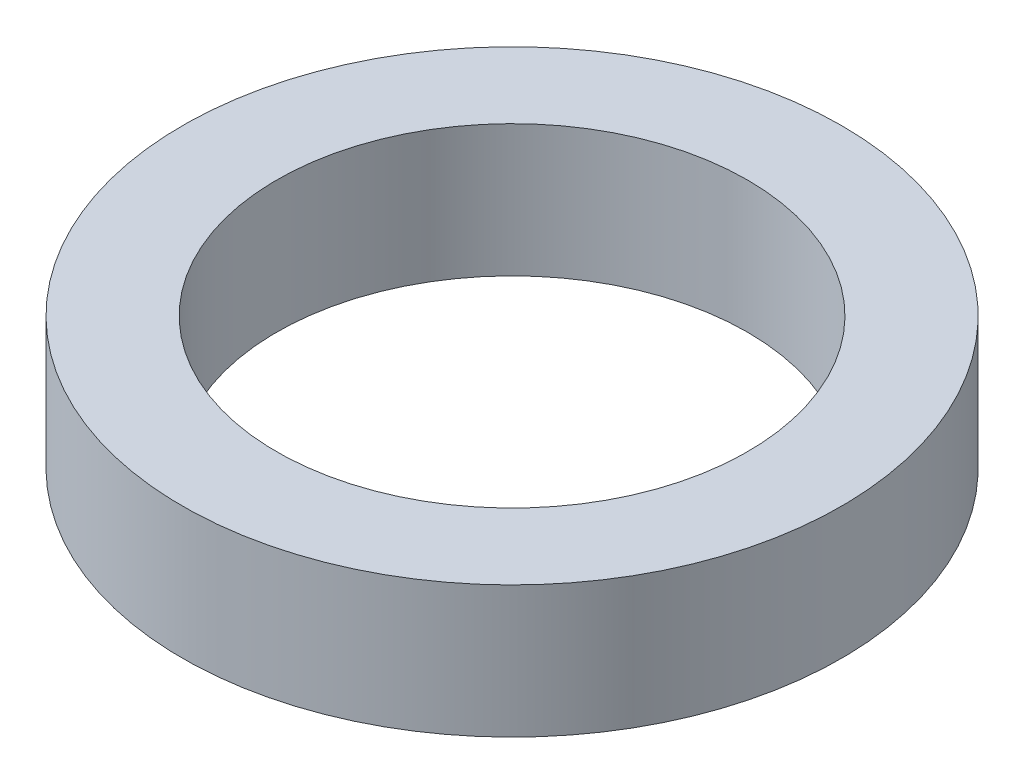
SolidWorks part; units mm, degrees
ref_plane "Front Plane" through (0, 0, 0) normal (0, 0, 1) x (1, 0, 0)
ref_plane "Top Plane" through (0, 0, 0) normal (0, 1, 0) x (1, 0, 0)
ref_plane "Right Plane" through (0, 0, 0) normal (1, 0, 0) x (0, 0, -1)
sketch "Sketch1" plane through (0, 0, 0) normal (0, 1, 0) x (1, 0, 0)
  circle A0 centre (0, 0) radius 52.5
  dimension "FLANGE_OD" = 105
extrude "Boss-Extrude1" add sketch "Sketch1" along normal blind 21
sketch "Sketch2" plane through (0, 0, 0) normal (0, 1, 0) x (1, 0, 0)
  circle A0 centre (0, 0) radius 37.5
  dimension "BORE_D" = 75
extrude "Cut-Extrude1" cut sketch "Sketch2" along normal through all
sketch "Sketch3" plane through (0, 21, 0) normal (0, 1, 0) x (1, 0, 0)
  circle A0 centre (0, 0) radius 21.906 construction
  circle A1 centre (-21.906, 0) radius 2.4306
  dimension "BOLT_D" = 4.8612
  dimension "BOLT_PCD" = 43.8121
extrude "Cut-Extrude2" cut sketch "Sketch3" against normal blind 18.8199 rebuild error yes
pattern_circular "CirPattern1" count 4 over 360 rebuild error yes
